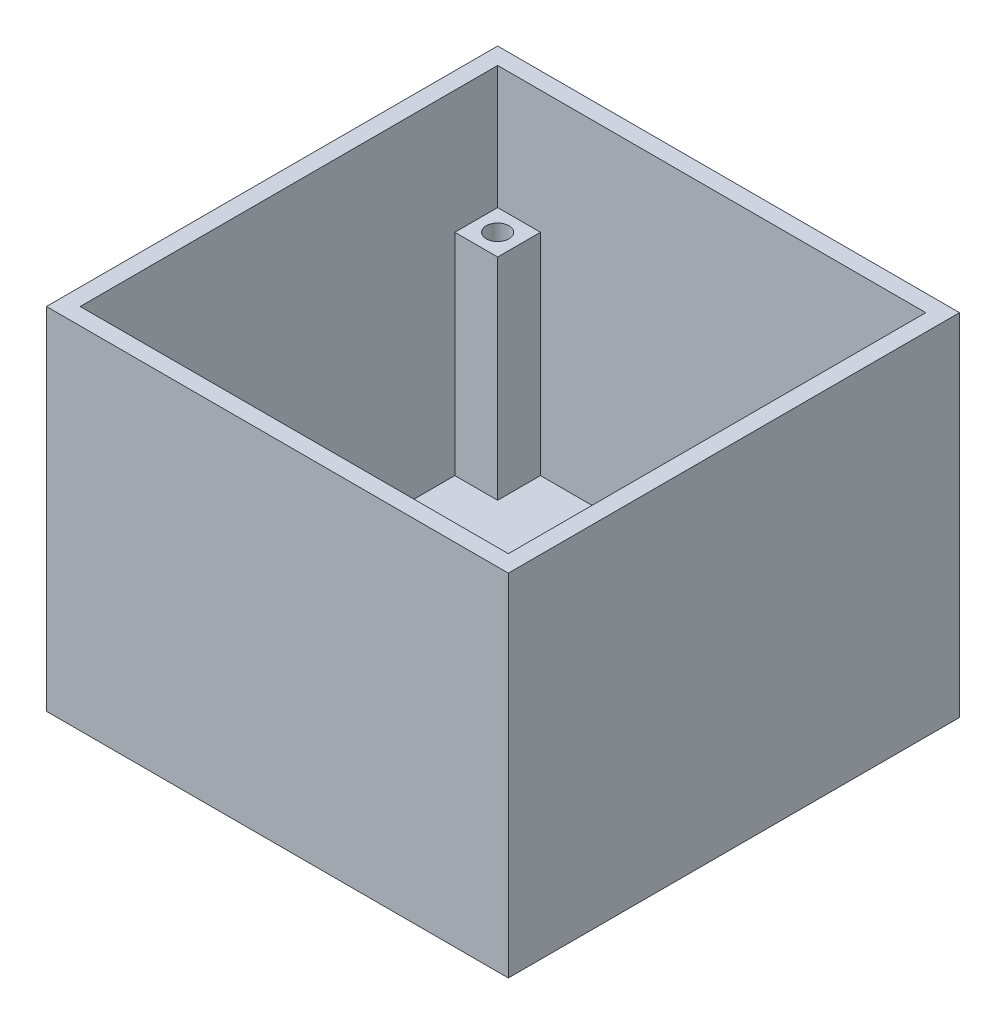
SolidWorks part; units mm, degrees
ref_plane "Front Plane" through (0, 0, 0) normal (0, 0, 1) x (1, 0, 0)
ref_plane "Top Plane" through (0, 0, 0) normal (0, 1, 0) x (1, 0, 0)
ref_plane "Right Plane" through (0, 0, 0) normal (1, 0, 0) x (0, 0, -1)
sketch "Sketch1" plane through (0, 0, 0) normal (0, 1, 0) x (1, 0, 0)
  line L1 (27.4, -26.765) -> (-27.4, -26.765)
  line L2 (27.4, -26.765) -> (27.4, 26.765)
  line L3 (27.4, 26.765) -> (-27.4, 26.765)
  line L4 (-27.4, -26.765) -> (-27.4, 26.765)
  line L5 (27.4, -26.765) -> (-27.4, 26.765) construction
  line L6 (27.4, 26.765) -> (-27.4, -26.765) construction
  point P0 (0, 0)
  dimension "D1" = 54.8
  dimension "D2" = 53.53
extrude "Boss-Extrude1" add sketch "Sketch1" along normal blind 41.6
sketch "Sketch2" plane through (0, 41.6, 0) normal (0, 1, 0) x (1, 0, 0)
  line L0 (-27.4, 26.765) -> (-27.4, -26.765) construction
  line L1 (25.4, -24.765) -> (-25.4, -24.765)
  line L2 (25.4, -24.765) -> (25.4, 24.765)
  line L3 (25.4, 24.765) -> (-25.4, 24.765)
  line L4 (-25.4, -24.765) -> (-25.4, 24.765)
  line L5 (25.4, -24.765) -> (-25.4, 24.765) construction
  line L6 (25.4, 24.765) -> (-25.4, -24.765) construction
  line L7 (27.4, 26.765) -> (-27.4, 26.765) construction
  point P0 (0, 0)
  dimension "D1" = 2
  dimension "D2" = 2
extrude "Cut-Extrude1" cut sketch "Sketch2" against normal blind 39.6
sketch "Sketch3" plane through (0, 2, 0) normal (0, 1, 0) x (1, 0, 0)
  line L1 (-25.4, 24.765) -> (-20.32, 24.765)
  line L2 (-25.4, 24.765) -> (-25.4, 19.685)
  line L3 (-25.4, 19.685) -> (-20.32, 19.685)
  line L4 (-20.32, 24.765) -> (-20.32, 19.685)
  line L5 (25.4, 24.765) -> (20.32, 24.765)
  line L6 (25.4, 24.765) -> (25.4, 19.685)
  line L7 (25.4, 19.685) -> (20.32, 19.685)
  line L8 (20.32, 24.765) -> (20.32, 19.685)
  line L9 (25.4, -24.765) -> (20.32, -24.765)
  line L10 (25.4, -24.765) -> (25.4, -19.685)
  line L11 (25.4, -19.685) -> (20.32, -19.685)
  line L12 (20.32, -24.765) -> (20.32, -19.685)
  dimension "D1" = 5.08
  dimension "D2" = 5.08
  dimension "D3" = 5.08
  dimension "D4" = 5.08
  dimension "D5" = 5.08
  dimension "D6" = 5.08
extrude "Boss-Extrude2" add sketch "Sketch3" along normal blind 25
sketch "Sketch4" plane through (0, 27, 0) normal (0, 1, 0) x (1, 0, 0)
  line L0 (-20.32, 19.685) -> (-20.32, 24.765) construction
  line L3 (-25.4, 19.685) -> (-20.32, 19.685) construction
  line L4 (20.32, 19.685) -> (25.4, 19.685) construction
  line L5 (20.32, 24.765) -> (20.32, 19.685) construction
  line L6 (25.4, -19.685) -> (20.32, -19.685) construction
  line L7 (20.32, -19.685) -> (20.32, -24.765) construction
  circle A0 centre (-22.86, 22.225) radius 1.35
  circle A1 centre (22.86, 22.225) radius 1.35
  circle A2 centre (22.86, -22.225) radius 1.35
  point P12 (22.86, -19.685)
  dimension "D1" = 2.54
  dimension "D3" = 2.54
  dimension "D5" = 2.54
  dimension "D2" = 2.54
  dimension "D4" = 2.54
  dimension "D6" = 2.54
extrude "Cut-Extrude2" cut sketch "Sketch4" against normal blind 10
